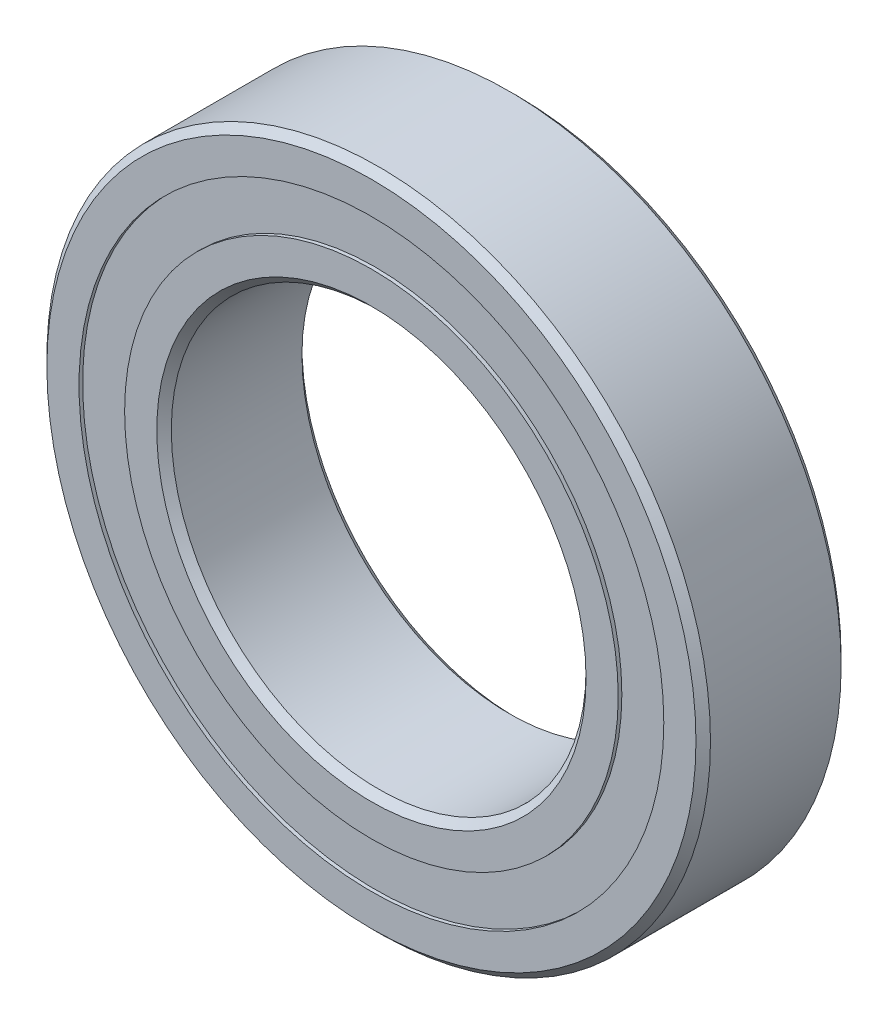
SolidWorks part; units mm, degrees
ref_plane "Front Plane" through (0, 0, 0) normal (0, 0, 1) x (1, 0, 0)
ref_plane "Top Plane" through (0, 0, 0) normal (0, 1, 0) x (1, 0, 0)
ref_plane "Right Plane" through (0, 0, 0) normal (1, 0, 0) x (0, 0, -1)
sketch "Sketch1" plane through (0, 0, 0) normal (1, 0, 0) x (0, 0, -1)
  line L0 (-3.5, 0) -> (3.5, 0) construction
  line L1 (0, 16) -> (0, -16) construction
  line L2 (3.15, 16) -> (-3.15, 16)
  line L3 (-3.15, 16) -> (-3.5, 15.65)
  line L4 (-3.5, 15.65) -> (-3.5, 14.0989)
  line L5 (-3.5, 14.0989) -> (-1.5556, 14.0989)
  line L6 (3.5, 14.0989) -> (1.5556, 14.0989)
  line L7 (3.5, 15.65) -> (3.5, 14.0989)
  line L8 (3.15, 16) -> (3.5, 15.65)
  line L9 (0, 16) -> (0, 13) construction
  line L10 (0, 13) -> (0, 10) construction
  arc A0 (-1.5556, 14.0989) -> (1.5556, 14.0989) centre (0, 13) cw
  point P14 (0, 10)
  dimension "Width" = 7
  dimension "OD" = 32
  dimension "D1" = 45
  dimension "D2" = 0.35
  dimension "Shaft Dia" = 20
  dimension "D3" = 3.1111
  dimension "D4" = 1.0989
revolve "Revolve1" add sketch "Sketch1" angle 360 about L0
sketch "Sketch3" plane through (0, 0, 0) normal (1, 0, 0) x (0, 0, -1)
  line L0 (-3.5, 11.9011) -> (-1.5556, 11.9011)
  line L1 (0, 16) -> (0, -16) construction
  line L2 (-3.5, 15.65) -> (-3.5, 14.0989) construction
  line L3 (-3.5, 11.9011) -> (-3.5, 10.35)
  line L4 (-3.15, 16) -> (-3.5, 15.65) construction
  line L5 (-3.5, 10.35) -> (-3.15, 10)
  line L6 (-3.15, 10) -> (3.15, 10)
  line L7 (3.15, 16) -> (3.15, -16) construction
  line L8 (3.15, 10) -> (3.5, 10.35)
  line L9 (3.5, -15.65) -> (3.5, 15.65) construction
  line L10 (3.5, 10.35) -> (3.5, 11.9011)
  line L11 (3.5, 11.9011) -> (1.5556, 11.9011)
  line L13 (3.15, 16) -> (3.5, 15.65) construction
  arc A0 (1.5556, 14.0989) -> (-1.5556, 14.0989) centre (0, 13) ccw construction
  arc A1 (1.5556, 11.9011) -> (-1.5556, 11.9011) centre (0, 13) cw
revolve "Revolve3" add sketch "Sketch3" angle 360 about L0
sketch "Sketch4" plane through (0, 0, 0) normal (1, 0, 0) x (0, 0, -1)
  line L0 (-1.9046, 13) -> (1.9046, 13)
  arc A2 (-1.9046, 13) -> (1.9046, 13) centre (0, 13) cw
  arc A3 (1.5556, 14.0989) -> (-1.5556, 14.0989) centre (0, 13) ccw construction
revolve "Revolve4" add sketch "Sketch4" angle 360 about L0
ref_axis "Axis1" through (0, 0, -3.5) along (0, 0, 1)
pattern_circular "CirPattern1" count 12 every 30 about axis through (0, 0, -3.5) along (0, 0, 1) of bodies 104
sketch "Sketch5" plane through (0, 0, 0) normal (1, 0, 0) x (0, 0, -1)
  line L0 (-3.5, 14.0989) -> (-1.5556, 14.0989) construction
  line L1 (-3.325, 14.0989) -> (-1.9046, 14.0989)
  line L2 (-3.325, 14.0989) -> (-3.325, 11.9011)
  line L3 (-3.325, 11.9011) -> (-1.9046, 11.9011)
  line L4 (-1.9046, 14.0989) -> (-1.9046, 11.9011)
  line L5 (-3.5, 11.9011) -> (-1.5556, 11.9011) construction
  line L6 (3.5, 14.0989) -> (1.5556, 14.0989) construction
  line L7 (3.325, 14.0989) -> (1.9046, 14.0989)
  line L8 (3.325, 14.0989) -> (3.325, 11.9011)
  line L9 (3.325, 11.9011) -> (1.9046, 11.9011)
  line L10 (1.9046, 14.0989) -> (1.9046, 11.9011)
  line L11 (3.5, 11.9011) -> (1.5556, 11.9011) construction
  line L12 (-3.15, 16) -> (-3.5, 15.65) construction
  point P18 (-3.325, 15.825)
revolve "Revolve5" add sketch "Sketch5" angle 360 about L0
equation "\"D2@Sketch1\" = \"Width@Sketch1\"*.05"
equation "\"D3@Sketch1\" = \"Width@Sketch1\"/2.25"
equation "\"D4@Sketch1\" = (((\"OD@Sketch1\"-\"Width@Sketch1\")/2)/3.25)/3.5"
equation "\"D2@CirPattern1\" = 360/\"Balls@CirPattern1\""
